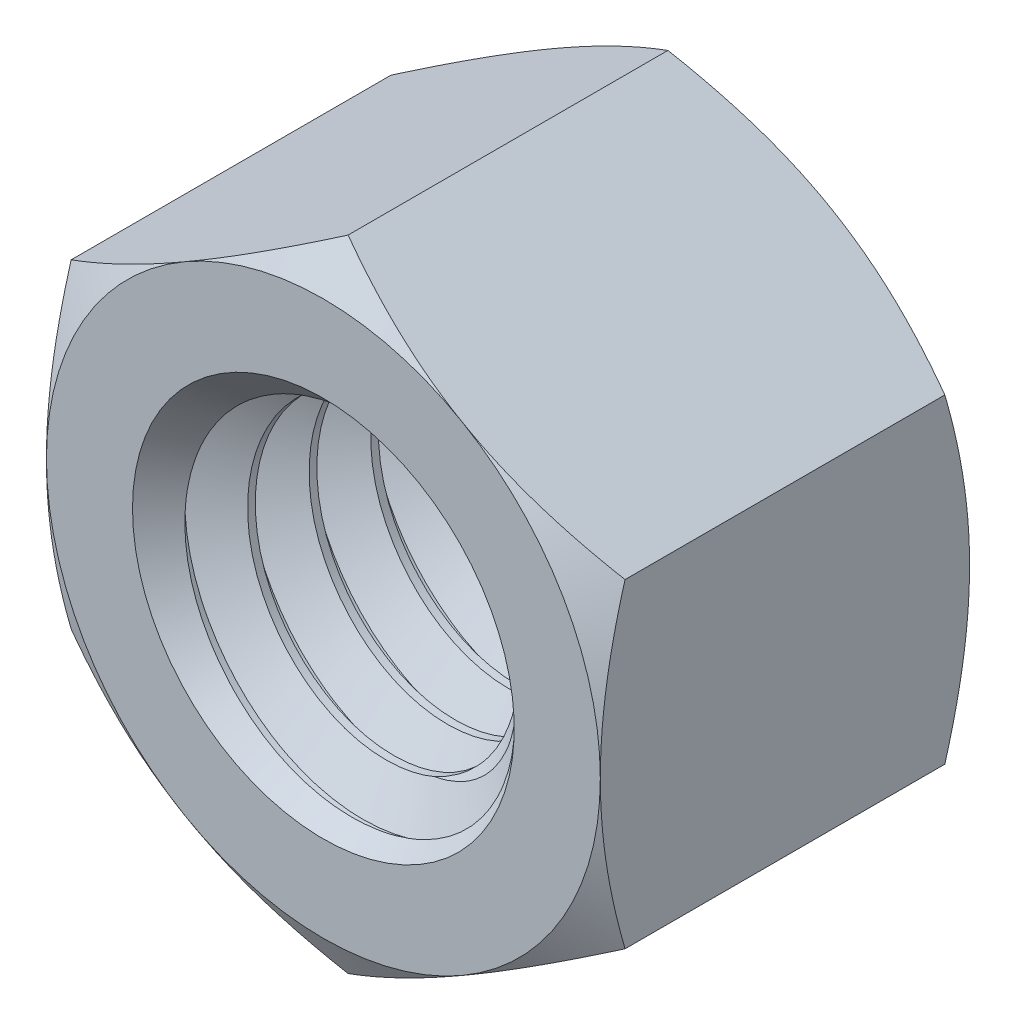
SolidWorks part; units mm, degrees
ref_plane "Front Plane" through (0, 0, 0) normal (0, 0, 1) x (1, 0, 0)
ref_plane "Top Plane" through (0, 0, 0) normal (0, 1, 0) x (1, 0, 0)
ref_plane "Right Plane" through (0, 0, 0) normal (1, 0, 0) x (0, 0, -1)
sketch "Sketch3" plane through (0, 0, 0) normal (1, 0, 0) x (0, 0, -1)
  line L0 (-1.5, 0) -> (1.5, 0) construction
  line L1 (0, 2.25) -> (0, -2.25) construction
  line L2 (-1.5, 1.5) -> (-1.5, -1.5) construction
  point P2 (-11.2, 0)
  point P3 (11.2, 0)
  dimension "D1" = 12.7
  dimension "Length" = 3
  dimension "Min Thread Length" = 12.7
  dimension "Thread Dia" = 3
  dimension "Hex" = 4.5
sketch "Sketch1" plane through (0, 0, 0) normal (0, 0, 1) x (1, 0, 0)
  line L1 (0, 2.5981) -> (-2.25, 1.299)
  line L2 (-2.25, 1.299) -> (-2.25, -1.299)
  line L3 (-2.25, -1.299) -> (0, -2.5981)
  line L4 (0, -2.5981) -> (2.25, -1.299)
  line L5 (2.25, -1.299) -> (2.25, 1.299)
  line L6 (2.25, 1.299) -> (0, 2.5981)
  circle A0 centre (0, 0) radius 2.25 construction
  circle A1 centre (0, 0) radius 1.5
extrude "Extrude1" add sketch "Sketch1" along normal up to vertex (1.5 mm away) and the other way up to vertex (1.5 mm away) up to point (0, 0, 1.5) other way up to point (0, 0, -1.5)
sketch "Sketch11" plane through (0, 0, -1.5) normal (0, 0, -1) x (-1, 0, 0)
  circle A0 centre (0, 0) radius 1.5 construction
  circle A1 centre (0, 0) radius 1.5
curve "Helix/Spiral1" pitch 0.5 height 3.5 radius 1.5 centre (0, 0, -1.5) axis (0, 0, 1) start towards (0, 1, 0) parameters "Pitch"=0.5
sketch "Sketch12" plane through (0, 0, 0) normal (1, 0, 0) x (0, 0, -1)
  line L0 (1.9375, 1.5) -> (1.5, 1.5)
  line L1 (1.9375, 1.5) -> (1.75, 1.1752)
  line L2 (1.75, 1.1752) -> (1.6875, 1.1752)
  line L3 (1.6875, 1.1752) -> (1.5, 1.5)
  line L4 (1.7187, 1.1752) -> (1.7187, 1.5) construction
  line L5 (1.8438, 1.3376) -> (1.5937, 1.3376) construction
  dimension "D1" = 0.0625
  dimension "D2" = 0.25
  dimension "D3" = 60
sweep "Sweep1" add profiles "Sketch12" path "Helix/Spiral1"
sketch "Sketch6" plane through (0, 0, -1.5) normal (0, 0, -1) x (-1, 0, 0)
  line L6 (0, 2.5981) -> (-2.25, 1.299)
  line L7 (-2.25, 1.299) -> (-2.25, -1.299)
  line L8 (-2.25, -1.299) -> (0, -2.5981)
  line L9 (0, -2.5981) -> (2.25, -1.299)
  line L10 (2.25, -1.299) -> (2.25, 1.299)
  line L11 (2.25, 1.299) -> (0, 2.5981)
  line L12 (0, 2.5981) -> (-2.25, 1.299)
  line L13 (-2.25, 1.299) -> (-2.25, -1.299)
  line L14 (-2.25, -1.299) -> (0, -2.5981)
  line L15 (0, -2.5981) -> (2.25, -1.299)
  line L16 (2.25, -1.299) -> (2.25, 1.299)
  line L17 (2.25, 1.299) -> (0, 2.5981)
  dimension "D1" = 0
extrude "Extrude2" cut sketch "Sketch6" along normal through all
sketch "Sketch7" plane through (0, 0, -1.5) normal (0, 0, -1) x (-1, 0, 0)
  circle A2 centre (0, 0) radius 1.5508
  circle A3 centre (0, 0) radius 1.5508
  dimension "D1" = 0.0508
extrude "Extrude3" cut sketch "Sketch7" against normal through all draft 43
sketch "Sketch8" plane through (0, 0, -1.5) normal (0, 0, -1) x (-1, 0, 0)
  circle A0 centre (0, 0) radius 2.25 construction
  circle A1 centre (0, 0) radius 2.25
extrude "Extrude4" cut sketch "Sketch8" against normal through all draft 60 flip side to cut
mirror "Mirror1" about plane through (0, 0, 0) normal (0, 0, 1) of "Extrude2", "Extrude3", "Extrude4"
sketch "Sketch9" [suppressed] plane through (0, 0, 0) normal (1, 0, 0) x (0, 0, -1)
  line L1 (-12.7, 2.4638) -> (12.7, 2.4638)
  line L2 (-12.7, 2.4638) -> (-12.7, 0)
  line L3 (-12.7, 0) -> (12.7, 0)
  line L4 (12.7, 2.4638) -> (12.7, 0)
  line L7 (-25.4, 0) -> (25.4, 0) construction
revolve "Revolve" [suppressed] add sketch "Sketch9" angle 360 about L0
sketch "Sketch10" [suppressed] plane through (0, 0, 0) normal (1, 0, 0) x (0, 0, -1)
  line L0 (25.4, 2.413) -> (12.7, 2.413)
  line L1 (-25.4, 2.413) -> (-12.7, 2.413)
  line L2 (12.7, 2.413) -> (12.7, -2.413)
  line L3 (-25.4, -2.4638) -> (-12.7, -2.4638)
  line L4 (-12.7, 2.413) -> (-12.7, -2.4638)
  line L5 (12.7, -2.413) -> (25.4, -2.413)
sketch "Sketch13" plane through (0, 0, 1.5) normal (0, 0, 1) x (1, 0, 0)
  line L0 (0.6959, 0.4402) -> (1.0897, 0.4402) construction
  line L1 (0.6959, 0.4402) -> (0.6959, -0.3853) construction
  line L2 (0.6959, 0.4402) -> (3.8103, 3.3481) construction
  arc A0 (0.5013, -1.063) -> (1.1082, -0.3912) centre (0, 0) ccw construction
  point P0 (0.6959, 0.4402)
  point P8 (-11.7542, 6.7404)
  point P9 (3.8103, 3.3481)
  point P10 (3.8103, 3.3481)
  point P11 (1.0897, 0.4402)
equation "\"D1@Sketch3\" = \"Min Thread Length@Sketch3\""
equation "\"D3@Helix/Spiral1\" = \"Length@Sketch3\"+\"Pitch@Helix/Spiral1\""
equation "\"D1@Sketch12\" = \"Pitch@Helix/Spiral1\"*.125"
equation "\"D2@Sketch12\" = \"Pitch@Helix/Spiral1\"*.5"
